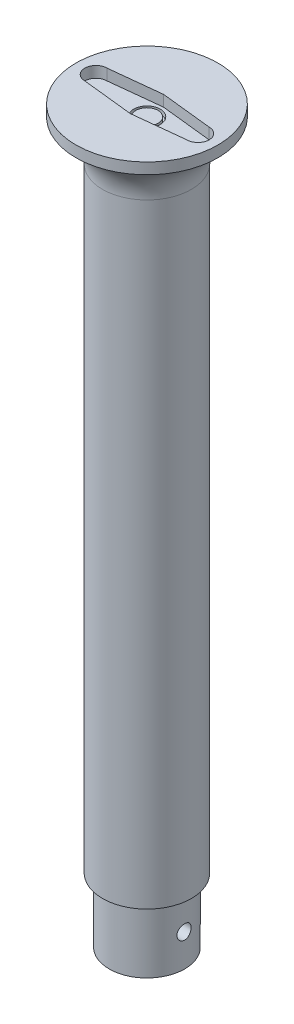
SolidWorks part; units mm, degrees
ref_plane "Front Plane" through (0, 0, 0) normal (0, 0, 1) x (1, 0, 0)
ref_plane "Top Plane" through (0, 0, 0) normal (0, 1, 0) x (1, 0, 0)
ref_plane "Right Plane" through (0, 0, 0) normal (1, 0, 0) x (0, 0, -1)
sketch "Sketch1" plane through (0, 0, 0) normal (0, 1, 0) x (1, 0, 0)
  line L0 (-10, 0) -> (10, 0)
  circle A0 centre (0, 0) radius 10
  dimension "D1" = 20
extrude "Boss-Extrude1" add sketch "Sketch1" along normal blind 150 contours A0
sketch "Sketch2" plane through (0, 0, 0) normal (0, -1, 0) x (1, 0, 0)
  circle A0 centre (0, 0) radius 8.5
  circle A1 centre (0, 0) radius 4.5
  dimension "D1" = 4
extrude "Boss-Extrude2" add sketch "Sketch2" along normal blind 14.5 contours A0 A1 region at (-8.2596, 0, 0)
sketch "Sketch3" plane through (0, 0, 0) normal (1, 0, 0) x (0, 0, -1)
  line L0 (0, 0) -> (0, -14.5) construction
  line L1 (-8.5, -14.5) -> (8.5, -14.5) construction
  circle A0 centre (0, -7.25) radius 1.6
extrude "Cut-Extrude1" cut sketch "Sketch3" against normal blind 14.5 and the other way blind 14.5
sketch "Sketch5" plane through (0, 150, 0) normal (0, 1, 0) x (1, 0, 0)
  circle A0 centre (0, 0) radius 16
extrude "Boss-Extrude3" add sketch "Sketch5" against normal blind 2.5
fillet "Fillet1" radius 10 1 edges at (0, 147.5, 10)
sketch "Sketch4" plane through (0, 150, 0) normal (0, 1, 0) x (1, 0, 0)
  line L0 (-14, 0) -> (14, 0)
  line L1 (0, 0) -> (0, 3.8688)
  line L2 (-11.5, 2.5) -> (0, 3.75)
  line L3 (0, 3.75) -> (11.5, 2.5)
  line L4 (11.5, 2.5) -> (11.5, -2.5)
  line L5 (11.5, -2.5) -> (0, -3.75)
  line L6 (0, -3.75) -> (-11.5, -2.5)
  circle A0 centre (0, 0) radius 3.75
  circle A1 centre (11.5, 0) radius 2.5
  circle A2 centre (-11.5, 0) radius 2.5
  point P6 (0, 0)
  dimension "D1" = 28
extrude "Cut-Extrude2" cut sketch "Sketch4" against normal blind 2.5 contours A2 L0 | A2 L0 | L0 A2 L6 A0 | L2 A2 L0 A0 | L2 A0 L0 L1 | L5 A0 L0 L6 | L0 A0 L3 L1 | A1 L3 A0 L0 | A1 L0 A0 L5 | L0 A1 L4 | L4 A1 L0 | L0 A1 L4 | L4 A1 L0 region at (-11.5, 150, -1.061) region at (-11.5, 150, 1.061) region at (-6.2037, 150, -1.7083) region at (-6.2037, 150, 1.7083) region at (-1.5928, 150, -1.5893) region at (0, 150, 1.5893) region at (1.5928, 150, -1.5893) region at (6.2037, 150, -1.7083) region at (6.2037, 150, 1.7083) region at (10.439, 150, -1.061) region at (10.439, 150, 1.061) region at (12.561, 150, -1.061) region at (12.561, 150, 1.061)
sketch "Sketch6" plane through (0, 147.5, 0) normal (0, 1, 0) x (1, 0, 0)
  circle A0 centre (0, 0) radius 3
  circle A1 centre (0, 0) radius 2.5
extrude "Cut-Extrude3" cut sketch "Sketch6" against normal blind 1
